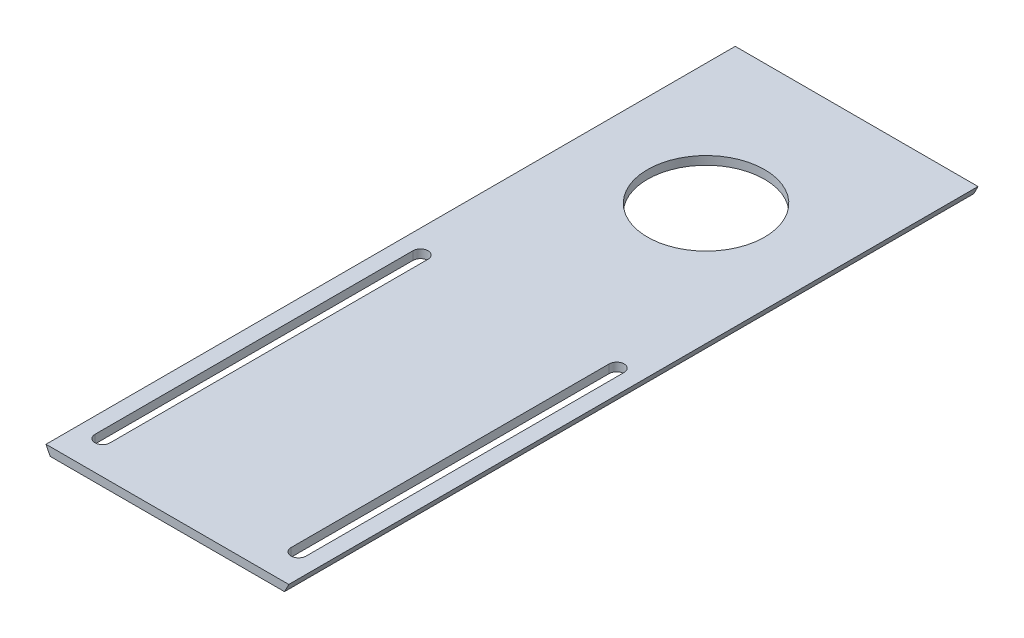
SolidWorks part; units mm, degrees
material "Brass"
ref_plane "Front Plane" through (0, 0, 0) normal (0, 0, 1) x (1, 0, 0)
ref_plane "Top Plane" through (0, 0, 0) normal (0, 1, 0) x (1, 0, 0)
ref_plane "Right Plane" through (0, 0, 0) normal (1, 0, 0) x (0, 0, -1)
sketch "Sketch2" plane through (0, 0, 0) normal (0, 0, 1) x (1, 0, 0)
  line L1 (0, -21.393) -> (0, -24.5934) construction
  line L2 (-44.45, -24.5934) -> (44.45, -24.5934)
  line L4 (-46.0758, -21.393) -> (46.0758, -21.393)
  arc A1 (-46.0758, -21.393) -> (-44.45, -24.5934) centre (0, 0) ccw
  arc A3 (44.45, -24.5934) -> (46.0758, -21.393) centre (0, 0) ccw
  dimension "D2" = 3.2004
extrude "Boss-Extrude1" add sketch "Sketch2" along normal blind 261.62 contours L4 A3 L2 A1
sketch "Sketch3" plane through (0, -24.5934, 0) normal (0, -1, 0) x (1, 0, 0)
  line L0 (-44.45, 57.15) -> (44.45, 57.15) construction
  line L1 (44.45, 261.62) -> (44.45, 0) construction
  line L2 (-44.45, 261.62) -> (-44.45, 0) construction
  line L3 (-44.45, 261.62) -> (44.45, 261.62) construction
  line L4 (0, 57.15) -> (0, 0) construction
  line L5 (-44.45, 0) -> (44.45, 0) construction
  line L6 (-40.0535, 128.3174) -> (-34.3859, 128.3174) construction
  line L7 (-40.0535, 128.3174) -> (-40.0535, 249.024)
  line L8 (-40.0535, 249.024) -> (-34.3859, 249.024) construction
  line L9 (-34.3859, 128.3174) -> (-34.3859, 249.024)
  line L10 (-37.2197, 261.62) -> (-37.2197, 251.8579) construction
  line L11 (-40.0535, 188.6707) -> (-44.45, 188.6707) construction
  line L12 (34.3859, 128.3174) -> (40.0535, 128.3174) construction
  line L13 (34.3859, 128.3174) -> (34.3859, 249.024)
  line L14 (34.3859, 249.024) -> (40.0535, 249.024) construction
  line L15 (40.0535, 128.3174) -> (40.0535, 249.024)
  line L16 (37.2197, 261.62) -> (37.2197, 251.8579) construction
  line L17 (44.45, 188.6707) -> (40.0535, 188.6707) construction
  circle A0 centre (0, 57.15) radius 22.225
  arc A1 (-40.0535, 249.024) -> (-34.3859, 249.024) centre (-37.2197, 249.024) cw
  arc A2 (-34.3859, 128.3174) -> (-40.0535, 128.3174) centre (-37.2197, 128.3174) cw
  arc A3 (34.3859, 249.024) -> (40.0535, 249.024) centre (37.2197, 249.024) cw
  arc A4 (40.0535, 128.3174) -> (34.3859, 128.3174) centre (37.2197, 128.3174) cw
  dimension "D1" = 44.45
  dimension "D2" = 57.15
  dimension "D3" = 120.7066
  dimension "D4" = 5.6676
  dimension "D5" = 9.7621
  dimension "D6" = 4.3965
  dimension "D7" = 120.7066
  dimension "D8" = 5.6676
  dimension "D9" = 9.7621
  dimension "D10" = 4.3965
extrude "Cut-Extrude1" cut sketch "Sketch3" against normal through all
